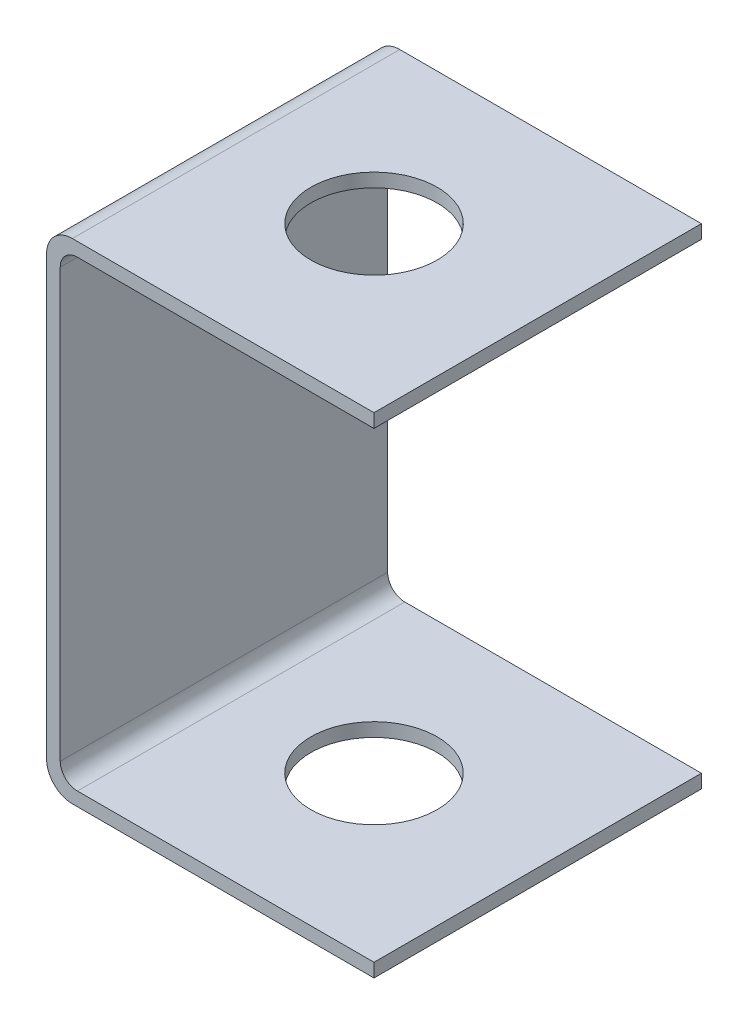
SolidWorks part; units mm, degrees
ref_plane "Front Plane" through (0, 0, 0) normal (0, 0, 1) x (1, 0, 0)
ref_plane "Top Plane" through (0, 0, 0) normal (0, 1, 0) x (1, 0, 0)
ref_plane "Right Plane" through (0, 0, 0) normal (1, 0, 0) x (0, 0, -1)
sketch "Sketch1" plane through (0, 0, 0) normal (0, 0, 1) x (1, 0, 0)
  line L0 (-17.4625, 55.3875) -> (19.05, 55.3875)
  line L1 (19.05, 55.3875) -> (19.05, 56.975)
  line L2 (19.05, 56.975) -> (-19.05, 56.975)
  line L3 (-19.05, 56.975) -> (-19.05, 0)
  line L4 (-19.05, 0) -> (19.05, 0)
  line L5 (19.05, 0) -> (19.05, 1.5875)
  line L6 (19.05, 1.5875) -> (-17.4625, 1.5875)
  line L7 (-17.4625, 1.5875) -> (-17.4625, 55.3875)
  point P7 (0, 0)
  dimension "D1" = 1.5875
  dimension "D2" = 1.5875
  dimension "D3" = 1.5875
  dimension "D4" = 38.1
  dimension "D5" = 53.8
extrude "Boss-Extrude1" add sketch "Sketch1" along normal blind 38.1
sketch "Sketch3" plane through (0, 0, 0) normal (0, 1, 0) x (1, 0, 0)
  circle A0 centre (0, -19.05) radius 7.35
  dimension "D2" = 14.7
  dimension "D1" = 19.05
extrude "Cut-Extrude1" cut sketch "Sketch3" along normal through all
fillet "Fillet1" radius 2 2 edges at (-17.4625, 1.5875, 19.05) (-17.4625, 55.3875, 19.05)
fillet "Fillet2" radius 3 2 edges at (-19.05, 0, 19.05) (-19.05, 56.975, 19.05)
equation "\"boltDiameter\" = 1in / 2"
equation "\"sleeveHeight\"= 2in"
equation "\"bracketThickness\"= 1in / 16"
equation "\"D1@Sketch1\"=\"bracketThickness\""
equation "\"D2@Sketch1\"=\"bracketThickness\""
equation "\"D3@Sketch1\"=\"bracketThickness\""
equation "\"D5@Sketch1\"=\"sleeveHeight\"+3mm"
equation "\"D2@Sketch3\"=\"boltDiameter\"+2mm"
